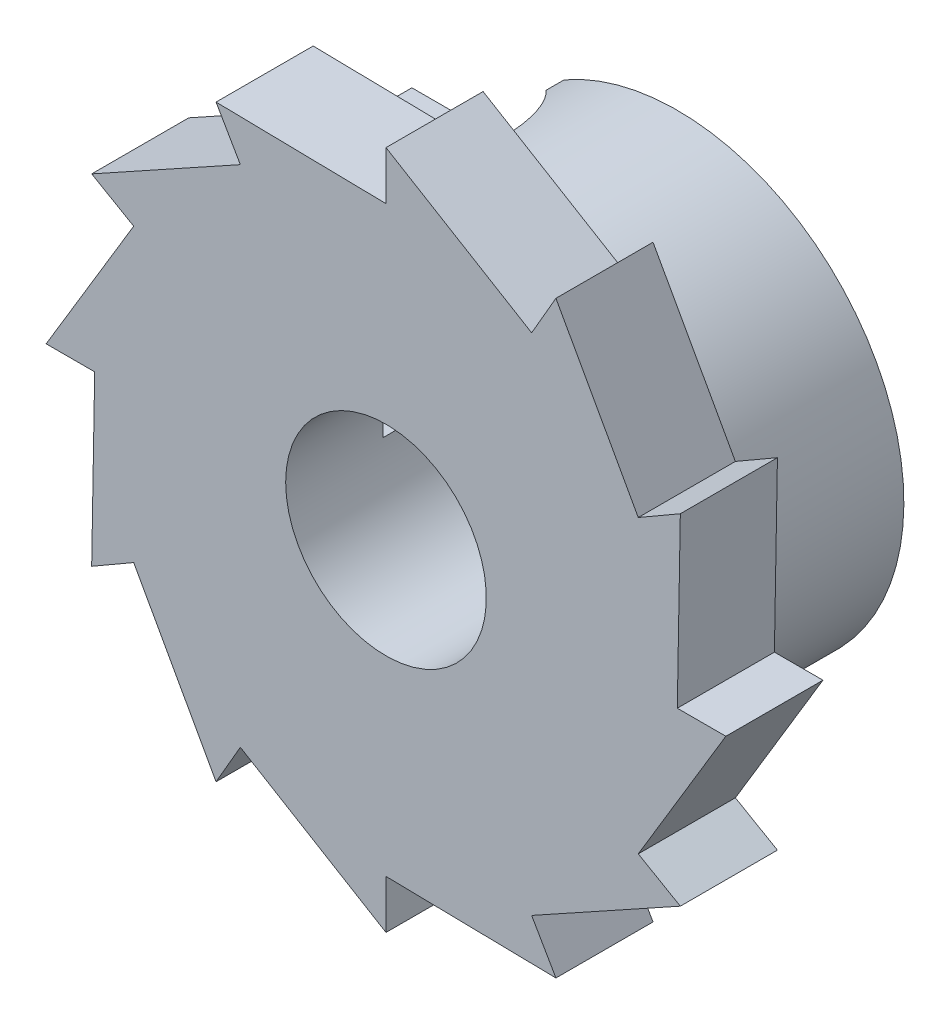
SolidWorks part; units mm, degrees
ref_plane "Front Plane" through (0, 0, 0) normal (0, 0, 1) x (1, 0, 0)
ref_plane "Top Plane" through (0, 0, 0) normal (0, 1, 0) x (1, 0, 0)
ref_plane "Right Plane" through (0, 0, 0) normal (1, 0, 0) x (0, 0, -1)
sketch "Sketch1" plane through (0, 0, 0) normal (0, 0, 1) x (1, 0, 0)
  line L0 (0, 9) -> (0, 10.5)
  line L1 (0.0027, 10.5) -> (-49999.9973, 10.5) construction
  line L2 (0, 0) -> (0, 50000) construction
  line L3 (-0.0178, -0.0309) -> (24999.9822, 43301.2393) construction
  line L4 (0, 9) -> (0, 3.1)
  line L5 (4.5, 7.7942) -> (1.55, 2.6847)
  line L6 (4.5, 7.7942) -> (0, 10.5)
  circle A0 centre (0, 0) radius 9 construction
  circle A1 centre (0, 0) radius 3.1 construction
  arc A2 (0, 10.5) -> (4.5, 7.7942) centre (0, 5.4051) cw construction
  arc A3 (0, 3.1) -> (1.55, 2.6847) centre (0, 0) cw
  dimension "D1" = 6.2
  dimension "D2" = 18
  dimension "D3" = 30
  dimension "D4" = 1.5
extrude "Boss-Extrude1" add sketch "Sketch1" along normal blind 3
pattern_circular "CirPattern1" count 12 over 360 about axis through (0, 0, 3) along (0, 0, -1) of "Boss-Extrude1"
sketch "Sketch3" plane through (0, 0, 0) normal (0, 0, -1) x (-1, 0, 0)
  line L0 (7, -3.5) -> (7, -7)
  line L2 (-7, 0) -> (-7, 7)
  line L3 (-7, 7) -> (7, 7)
  line L5 (7, -7) -> (0, -7)
  line L7 (8.2, 3.5) -> (8.2, -3.5)
  line L8 (8.2, -3.5) -> (7, -3.5)
  line L9 (7, 0) -> (50007, 0) construction
  line L10 (7, 7) -> (8.2, 7)
  line L11 (8.2, 7) -> (8.2, 3.5)
  arc A0 (7, 0) -> (0, -7) centre (0, 0) ccw construction
  arc A1 (0, -7) -> (-7, 0) centre (0, 0) cw
  circle A2 centre (0, 0) radius 3.1
  circle A3 centre (0, 0) radius 3.1 construction
  point P14 (8.2, 0)
  dimension "D1" = 14
  dimension "D2" = 8.2
extrude "Boss-Extrude2" add sketch "Sketch3" along normal blind 6
sketch "Sketch4" plane through (0, 7, 0) normal (0, 1, 0) x (1, 0, 0)
  line L0 (-3.1, 0) -> (3.1, 0) construction
  line L1 (-3.1, 0) -> (3.1, 0) construction
  line L2 (-3.1, 0) -> (-3.1, -50000) construction
  line L4 (-8.2, 3) -> (-3.1, 3) construction
  line L8 (-8.2, 6) -> (-8.2, 0) construction
  circle A1 centre (-5.65, 3) radius 1.5
  point P10 (0, 0)
  point P11 (-5.65, 3)
  point P12 (0, 0)
  dimension "D1" = 3
sketch "Sketch6" plane through (-8.2, 0, 0) normal (-1, 0, 0) x (0, 0, 1)
  line L0 (0, 0) -> (-50000, 0) construction
  line L1 (-6, -0.3) -> (-6, 0.3)
  line L2 (-6, -7) -> (-6, -3.5) construction
  line L3 (-6, 0.3) -> (0, 0.3)
  line L10 (-6, -0.3) -> (0, -0.3)
  line L11 (0, -3.5) -> (0, 3.8252) construction
  line L12 (0, 0.3) -> (0, -0.3)
  point P12 (-0.5, 0)
  dimension "D4" = 0.3
sketch "Sketch9" plane through (0, 7, 0) normal (0, 1, 0) x (1, 0, 0)
  circle A0 centre (-5.65, 3) radius 1.75
  point P0 (-5.65, 3)
  dimension "D1" = 3.5
sketch "Sketch10" plane through (0, 7, 0) normal (0, 1, 0) x (1, 0, 0)
  line L0 (-3.5, 6) -> (-3.5, 5.4372)
  line L1 (-3.5, 0.5628) -> (-3.5, 0)
  line L3 (-3.5, 0) -> (-4.5, 0)
  line L4 (-3.5, 6) -> (-4.5, 6)
  line L5 (-8.2, 6) -> (7, 6) construction
  line L6 (-6.9, 6) -> (-4.5, 6)
  line L7 (-8.2, 6) -> (-8.2, 0) construction
  line L8 (-8.2, 5.0149) -> (-8.2, 0.9851)
  line L9 (-5.9339, 0) -> (6.4095, 0) construction
  line L10 (-6.9, 0) -> (-4.5, 0)
  arc A1 (-6.9, 6) -> (-8.2, 5.0149) centre (-5.65, 3) ccw
  arc A2 (-8.2, 0.9851) -> (-6.9, 0) centre (-5.65, 3) ccw
  arc A3 (-3.5, 0.5628) -> (-3.5, 5.4372) centre (-5.65, 3) ccw
  point P0 (-5.65, 3)
  dimension "D1" = 6.5
extrude "Cut-Extrude19" cut sketch "Sketch6" against normal up to surface (5.1146 mm away) up to face at (-3.1, 0, 3)
extrude "Cut-Extrude12" cut sketch "Sketch4" against normal through all
extrude "Cut-Extrude20" cut sketch "Sketch9" against normal up to surface (6.7 mm away) up to face at (-5.65, 0.3, -1.5)
sketch "Sketch12" plane through (0, 0, -6) normal (0, 0, -1) x (-1, 0, 0)
  line L0 (0, 0) -> (50000, 0) construction
  line L1 (8.2, -3.5) -> (6.0622, -3.5) construction
  line L2 (0, -7) -> (7, -7) construction
  line L3 (8.2, 3.5) -> (6.0622, 3.5)
  line L4 (0, -7) -> (7, -7)
  line L5 (7, -7) -> (7, -3.5)
  line L6 (7, -3.5) -> (6.0622, -3.5)
  line L7 (8.2, 3.5) -> (8.2, 7)
  line L8 (8.2, 7) -> (-7, 7)
  line L9 (-7, 7) -> (-7, 0)
  arc A0 (0, -7) -> (6.0622, -3.5) centre (0, 0) ccw
  arc A1 (6.0622, 3.5) -> (-7, 0) centre (0, 0) ccw
  line M9 (8.2, 0.3) -> (8.2, 7)
  line M10 (8.2, 7) -> (-7, 7)
  line M11 (-7, 7) -> (-7, 0)
  line M13 (0, -7) -> (7, -7)
  line M14 (7, -7) -> (7, -3.5)
extrude "Cut-Extrude21" cut sketch "Sketch12" against normal up to surface (6 mm away) contours A1 L8 M11 | A1 L3 M9 M10 | A0 L6 M13 M14 region at (5.4364, 5.4364, -6) region at (-6.0019, 5.597, -6) region at (-5.2918, -5.7512, -6) up to face at (3.8947, -3.9244, 0)
extrude "Cut-Extrude22" cut sketch "Sketch10" against normal up to surface (3.5 mm away) up to face at (-6.9978, 3.5, -3)
equation "\"ratchetTeethCount\"= 12"
equation "\"D3@Sketch1\"=360/\"ratchetTeethCount\""
equation "\"D1@CirPattern1\"=\"ratchetTeethCount\""
equation "\"ratchetHeight\"=1.5"
equation "\"D4@Sketch1\"=\"ratchetHeight\""
equation "\"ratchetInnerDiameter\"= 18"
equation "\"D2@Sketch1\"=\"ratchetInnerDiameter\""
